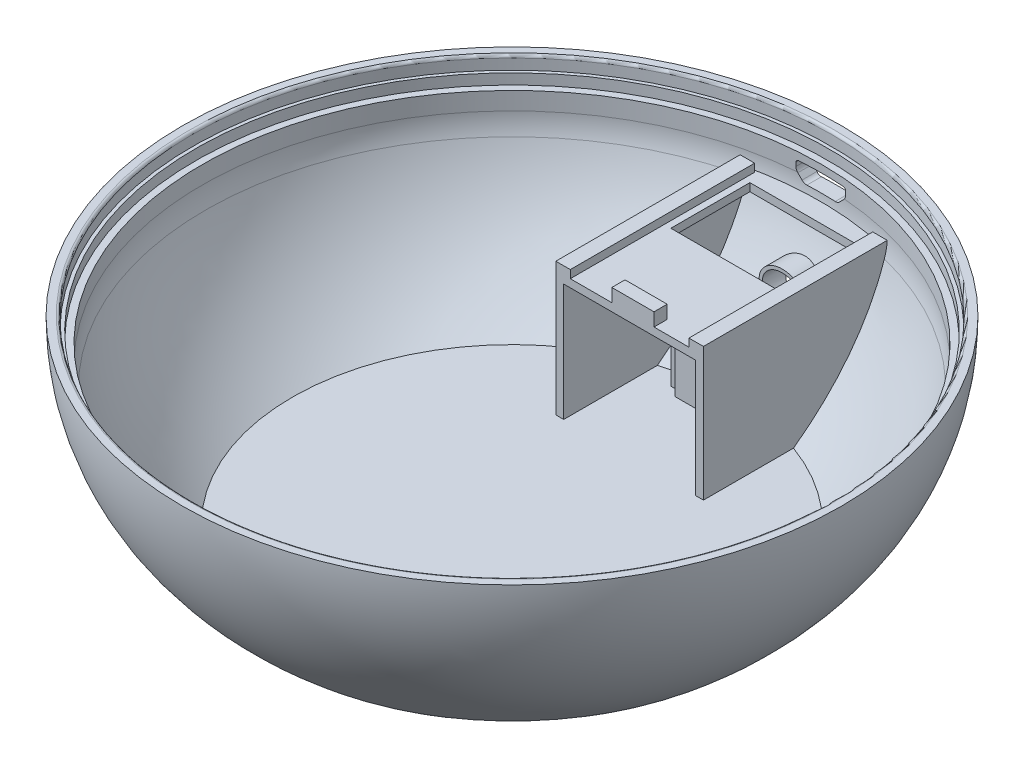
SolidWorks part; units mm, degrees
ref_plane "Plano frontal" through (0, 0, 0) normal (0, 0, 1) x (1, 0, 0)
ref_plane "Plano superior" through (0, 0, 0) normal (0, 1, 0) x (1, 0, 0)
ref_plane "Plano direito" through (0, 0, 0) normal (1, 0, 0) x (0, 0, -1)
sketch "Esboço1" plane through (0, 0, 0) normal (0, 0, 1) x (1, 0, 0)
  line L0 (0, 0) -> (0, -29.3333)
  line L1 (33.9935, -29.3333) -> (0, -29.3333)
  line L4 (0, 0) -> (50, 0)
  ellipse E0 centre (0, 0) end of major axis (-50, 0) minor radius 40 (33.9935, -29.3333) -> (50, 0) ccw
  dimension "D1" = 40
  dimension "D2" = 100
  dimension "D3" = 33.9935
revolve "Revolução1" add sketch "Esboço1" angle 360 about L0
shell "Casca1" thickness 2 removed face at (0, 0, 50)
sketch "Esboço7" plane through (0, 0, 0) normal (0, 1, 0) x (1, 0, 0)
  circle A0 centre (0, 0) radius 47
  circle A1 centre (0, 0) radius 48
  dimension "D1" = 94
extrude "Ressalto-extrusão3" add sketch "Esboço7" against normal up to next
sketch "Esboço9" plane through (0, 0, 0) normal (0, 1, 0) x (1, 0, 0)
  circle A0 centre (0, 0) radius 48.5
  dimension "D1" = 97
extrude "Corte-extrusão5" cut sketch "Esboço9" against normal blind 2
fillet "Filete3" radius 10 1 edges at (0, -7.7061, 47)
fillet "Filete4" radius 0.4 1 edges at (0, 0, 48.5)
fillet "Filete9" radius 6 1 edges at (0, -29.3333, 33.9935)
sketch "Esboço10" plane through (0, -2, 0) normal (0, 1, 0) x (1, 0, 0)
  circle A0 centre (0, 0) radius 48
  dimension "D1" = 96
extrude "Corte-extrusão6" cut sketch "Esboço10" against normal blind 1.6
sketch "Esboço15" plane through (0, 0, 0) normal (0, 0, 1) x (1, 0, 0)
  line L0 (0, -7.3333) -> (0, -4.7333) construction
  line L2 (-3.375, -4.7333) -> (3.375, -4.7333)
  line L3 (3.775, -5.1333) -> (3.775, -5.681)
  line L4 (3.4964, -6.3736) -> (2.8702, -7.0259)
  line L5 (2.1488, -7.3333) -> (-2.1488, -7.3333)
  line L6 (33.3248, -27.3333) -> (-33.3248, -27.3333) construction
  line L7 (-3.4964, -6.3736) -> (-2.8702, -7.0259)
  line L8 (-3.775, -5.1333) -> (-3.775, -5.681)
  arc A0 (2.8702, -7.0259) -> (2.1488, -7.3333) centre (2.1488, -6.3333) cw
  arc A1 (-2.8702, -7.0259) -> (-2.1488, -7.3333) centre (-2.1488, -6.3333) ccw
  arc A2 (3.775, -5.681) -> (3.4964, -6.3736) centre (2.775, -5.681) cw
  arc A3 (-3.4964, -6.3736) -> (-3.775, -5.681) centre (-2.775, -5.681) cw
  arc A4 (3.375, -4.7333) -> (3.775, -5.1333) centre (3.375, -5.1333) cw
  arc A5 (-3.775, -5.1333) -> (-3.375, -4.7333) centre (-3.375, -5.1333) cw
  point P14 (2.575, -7.3333)
  point P17 (-2.575, -7.3333)
  point P20 (3.775, -6.0833)
  point P23 (-3.775, -6.0833)
  point P26 (3.775, -4.7333)
  point P29 (-3.775, -4.7333)
  dimension "D6" = 1
  dimension "D7" = 0.4
  dimension "D1" = 7.55
  dimension "D2" = 2.6
  dimension "D3" = 1.35
  dimension "D4" = 5.15
  dimension "D5" = 20
extrude "Corte-extrusão9" cut sketch "Esboço15" against normal blind 62
ref_plane "Plano1" through (0, 0, -46.8482) normal (0, 0, -1) x (-1, 0, 0)
sketch "Esboço17" plane through (0, 0, -46.8482) normal (0, 0, -1) x (-1, 0, 0)
  line L0 (3.775, -5.681) -> (3.775, -5.1333) construction
  line L1 (11, -8.3333) -> (-11.4, -8.3333)
  line L2 (11, -8.3333) -> (11, -9.5333)
  line L3 (11, -9.5333) -> (-11.4, -9.5333)
  line L4 (-11.4, -8.3333) -> (-11.4, -9.5333)
  line L5 (-3.775, -5.1333) -> (-3.775, -5.681) construction
  line L7 (-3.375, -4.7333) -> (3.375, -4.7333) construction
  dimension "D1" = 1.2
  dimension "D2" = 7.225
  dimension "D3" = 22.4
  dimension "D4" = 3.6
  dimension "D5" = 7.625
extrude "Ressalto-extrusão4" add sketch "Esboço17" against normal blind 29.2
sketch "Esboço19" plane through (0, -9.5333, 0) normal (0, -1, 0) x (1, 0, 0)
  line L1 (-11, -17.6482) -> (-8.8, -17.6482)
  line L2 (-11, -17.6482) -> (-11, -45.6186)
  line L3 (-11, -45.6186) -> (-8.8, -45.6186)
  line L4 (-8.8, -17.6482) -> (-8.8, -45.6186)
  line L5 (11.4, -17.6482) -> (9.2, -17.6482)
  line L6 (11.4, -17.6482) -> (11.4, -45.5396)
  line L7 (11.4, -45.5396) -> (9.2, -45.5396)
  line L8 (9.2, -17.6482) -> (9.2, -45.5396)
  arc A0 (-11, -45.1386) -> (11.4, -45.0392) centre (0, 0) ccw construction
  dimension "D1" = 2.2
  dimension "D2" = 2.2
extrude "Ressalto-extrusão5" add sketch "Esboço19" against normal blind 2.4
sketch "Esboço20" plane through (0, -8.3333, 0) normal (0, 1, 0) x (1, 0, 0)
  line L0 (-8.8, 17.6482) -> (9.2, 17.6482) construction
  line L1 (-2.5, 17.6482) -> (3.9, 17.6482)
  line L2 (-2.5, 17.6482) -> (-2.5, 19.6482)
  line L3 (-2.5, 19.6482) -> (3.9, 19.6482)
  line L4 (3.9, 17.6482) -> (3.9, 19.6482)
  line L6 (-8.8, 17.6482) -> (-8.8, 45.6186) construction
  line L7 (9.2, 45.5396) -> (9.2, 17.6482) construction
  dimension "D1" = 2
  dimension "D2" = 6.3
  dimension "D3" = 6.4
  dimension "D4" = 5.3
extrude "Ressalto-extrusão6" add sketch "Esboço20" along normal blind 2
sketch "Esboço33" plane through (0, 0, 0) normal (0, 0, 1) x (1, 0, 0)
  ellipse E0 centre (0, -17.3333) end of major axis (-3, -17.3333) minor radius 2.5
  ellipse E1 centre (0, -17.3333) end of major axis (3.5, -17.3333) minor radius 3
  dimension "D1" = 3
  dimension "D2" = 6
  dimension "D3" = 2.5
  dimension "D4" = 7
sketch "Esboço24" plane through (0, 0, 0) normal (0, 0, 1) x (1, 0, 0)
  line L1 (9.2, -27.3333) -> (11.4, -27.3333) construction
  ellipse E0 centre (0, -17.3333) end of major axis (-3, -17.3333) minor radius 2.5
  dimension "D1" = 10
  dimension "D2" = 6
  dimension "D3" = 2.5
extrude "Corte-extrusão12" cut sketch "Esboço24" against normal up to next
ref_plane "Plano2" through (0, -9.5333, 0) normal (0, -1, 0) x (-1, 0, 0)
sketch "Esboço29" plane through (0, -9.5333, 0) normal (0, -1, 0) x (-1, 0, 0)
  line L0 (0, 16.1333) -> (0, -16.1333) construction
  line L1 (4.4, 31.9) -> (-4.4, 31.9)
  line L2 (4.4, 31.9) -> (4.4, 29.1)
  line L3 (4.4, 29.1) -> (-4.4, 29.1)
  line L4 (-4.4, 31.9) -> (-4.4, 29.1)
  line L5 (4.4, 31.9) -> (-4.4, 29.1) construction
  line L6 (4.4, 29.1) -> (-4.4, 31.9) construction
  point P0 (0, 30.5)
  dimension "D3" = 30.5
  dimension "D1" = 8.8
  dimension "D2" = 2.8
extrude "Ressalto-extrusão11" add sketch "Esboço29" along normal up to surface and the other way up to next up to face at (0, -27.3333, 33.3248)
sketch "Esboço30" plane through (0, -8.3333, 0) normal (0, 1, 0) x (1, 0, 0)
  line L1 (-7.8, 43.9) -> (8.2, 43.9)
  line L2 (-7.8, 43.9) -> (-7.8, 31.9)
  line L3 (-7.8, 31.9) -> (8.2, 31.9)
  line L4 (8.2, 43.9) -> (8.2, 31.9)
  line L5 (-7.8, 43.9) -> (8.2, 31.9) construction
  line L6 (-7.8, 31.9) -> (8.2, 43.9) construction
  line L7 (-8.8, 17.6482) -> (-8.8, 45.6186) construction
  line L8 (-4.4, 31.9) -> (4.4, 31.9) construction
  line L9 (9.2, 45.5396) -> (9.2, 17.6482) construction
  point P0 (0.2, 37.9)
  dimension "D1" = 16
  dimension "D2" = 12
  dimension "D3" = 0
  dimension "D4" = 1
  dimension "D5" = 1
extrude "Corte-extrusão13" cut sketch "Esboço30" against normal blind 4
sketch "Esboço27" plane through (0, 0, 0) normal (1, 0, 0) x (0, 0, -1)
  line L0 (40.7485, -21.3333) -> (30.1545, -21.3333)
  line L1 (30.1545, -21.3333) -> (30.1545, -27.3333)
  line L2 (30.1545, -27.3333) -> (33.7166, -27.7767)
  line L4 (31.9, -27.3333) -> (29.1, -27.3333) construction
  line L5 (33.7166, -27.7767) -> (37.7706, -25.4136)
  line L6 (37.7706, -25.4136) -> (39.1733, -23.8825)
  line L7 (39.1733, -23.8825) -> (40.7485, -21.3333)
  line L8 (40.9291, -19.8333) -> (43.4209, -19.8333) construction
  dimension "D1" = 1.5
extrude "Ressalto-extrusão9" add sketch "Esboço27" along normal blind 6 and the other way blind 6
sketch "Esboço31" plane through (0, -9.5333, 0) normal (0, -1, 0) x (1, 0, 0)
  line L1 (-11, -17.6482) -> (-9.8, -17.6482)
  line L2 (-11, -17.6482) -> (-11, -45.4156)
  line L3 (-11, -45.4156) -> (-9.8, -45.4156)
  line L4 (-9.8, -17.6482) -> (-9.8, -45.4156)
  line L5 (11.4, -17.6482) -> (10.2, -17.6482)
  line L6 (11.4, -17.6482) -> (11.4, -45.3274)
  line L7 (11.4, -45.3274) -> (10.2, -45.3274)
  line L8 (10.2, -17.6482) -> (10.2, -45.3274)
  arc A0 (-11, -45.14) -> (11.4, -45.0406) centre (0, 0) ccw construction
  dimension "D1" = 1.2
  dimension "D4" = 1.2
extrude "Ressalto-extrusão12" add sketch "Esboço31" along normal up to next
extrude "Ressalto-extrusão13" add sketch "Esboço33" against normal up to next from offset 41 offset against normal yes
